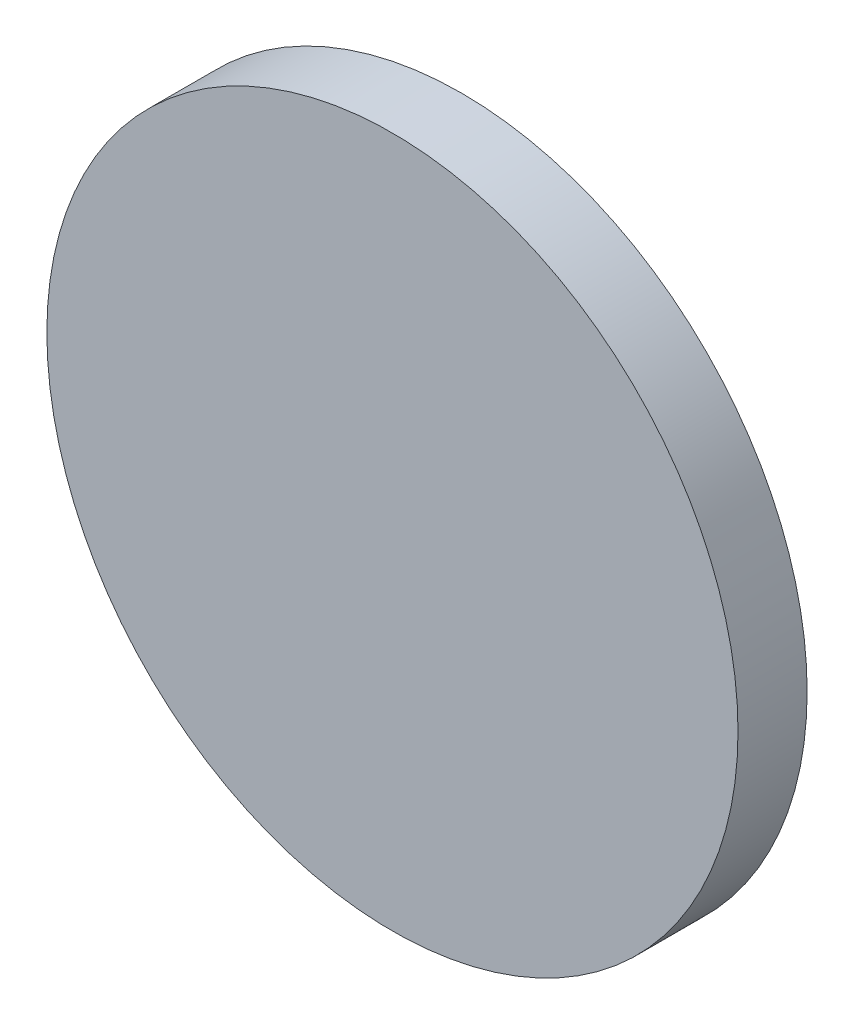
SolidWorks part; units mm, degrees
ref_plane "Front" through (0, 0, 0) normal (0, 0, 1) x (1, 0, 0)
ref_plane "Top" through (0, 0, 0) normal (0, 1, 0) x (1, 0, 0)
ref_plane "Right" through (0, 0, 0) normal (1, 0, 0) x (0, 0, -1)
sketch "Sketch1" plane through (0, 0, 0) normal (0, 0, 1) x (1, 0, 0)
  circle A0 centre (0, 0) radius 40.5646
extrude "Boss-Extrude1" add sketch "Sketch1" along normal blind 10
sketch "Sketch2" plane through (0, 0, 0) normal (0, 0, -1) x (-1, 0, 0)
  arc A0 (18.6051, 17.5721) -> (24.214, 8.2831) centre (20.3838, 12.3082) cw
  arc A1 (25.3393, 3.5846) -> (24.214, 8.2831) centre (0, 0) ccw construction
  arc A2 (24.214, 8.2831) -> (24.5204, -7.3264) centre (0, 0) cw
  arc A4 (24.5204, -7.3264) -> (19.2804, -16.8284) centre (20.8512, -11.4988) cw
  arc A5 (19.2804, -16.8284) -> (5.9153, -24.8985) centre (0, 0) cw
  arc A6 (5.9153, -24.8985) -> (-4.9336, -25.1115) centre (0.4673, -23.807) cw
  arc A7 (-4.9336, -25.1115) -> (-18.6051, -17.5721) centre (0, 0) cw
  arc A8 (-18.6051, -17.5721) -> (-24.214, -8.2831) centre (-20.3838, -12.3082) cw
  arc A9 (-24.214, -8.2831) -> (-24.5204, 7.3264) centre (0, 0) cw
  arc A10 (-24.5204, 7.3264) -> (-19.2804, 16.8284) centre (-20.8512, 11.4988) cw
  arc A11 (-19.2804, 16.8284) -> (-5.9153, 24.8985) centre (0, 0) cw
  arc A12 (-5.9153, 24.8985) -> (4.9336, 25.1115) centre (-0.4673, 23.807) cw
  arc A13 (4.9336, 25.1115) -> (18.6051, 17.5721) centre (0, 0) cw
  point P37 (0, 0)
  dimension "D1" = 6
extrude "Boss-Extrude2" add sketch "Sketch2" along normal blind 5.38
ref_plane "Plane1" through (0, 0, 0) normal (0.9998, -0.0196, 0) x (0, 0, -1)
sketch "Sketch4" plane through (0, 0, 0) normal (0.9998, -0.0196, 0) x (0, 0, -1)
  line L2 (0.1535, 36.0926) -> (0.1535, 40.6031)
  line L3 (0.1535, 40.6031) -> (-4.4167, 40.6031)
  line L4 (-4.4167, 40.6031) -> (-4.4167, 35.5144)
  line L6 (-4.4167, 35.8431) -> (-4.4167, -35.8431) construction
  line L7 (-4.4167, 35.5144) -> (-3.556, 32.3948)
  line L8 (-3.556, 32.4639) -> (-3.556, -32.4639) construction
  line L9 (-3.556, 32.3948) -> (-3.556, 29.3278)
  line L10 (-3.556, 29.3278) -> (0.6578, 29.3011)
  line L11 (7.3152, 29.3011) -> (-1.016, 29.3011) construction
  line L12 (0.6578, 29.3011) -> (0.1535, 36.0926)
ref_axis "Axis1" through (0, 0, 95.7757) along (0, 0, -1)
revolve "Cut-Revolve2" cut sketch "Sketch4" angle 360 about axis through (0, 0, 95.7757) along (0, 0, -1)
sketch "Sketch5" plane through (0, 0, 10) normal (0, 0, 1) x (1, 0, 0)
  circle A0 centre (0, 0) radius 76.2
extrude "Boss-Extrude3" add sketch "Sketch5" against normal up to surface (5.5833 mm away) up to face at (0, -35.5144, 4.4167)
extrude "Boss-Extrude4" add sketch "Sketch5<2>" along normal blind 9.66
sketch "Sketch5<2>" plane through (0, 0, 10) normal (0, 0, 1) x (1, 0, 0) same geometry as "Sketch5"
sketch "Sketch6" plane through (0, 0, 0) normal (0.9998, -0.0196, 0) x (0, 0, -1)
  line L1 (-19.66, 76.2) -> (-12.0338, 76.2)
  line L2 (-19.66, 76.2) -> (-19.66, 83.8262)
  line L3 (-19.66, 83.8262) -> (-12.0338, 83.8262)
  line L4 (-12.0338, 76.2) -> (-12.0338, 83.8262)
